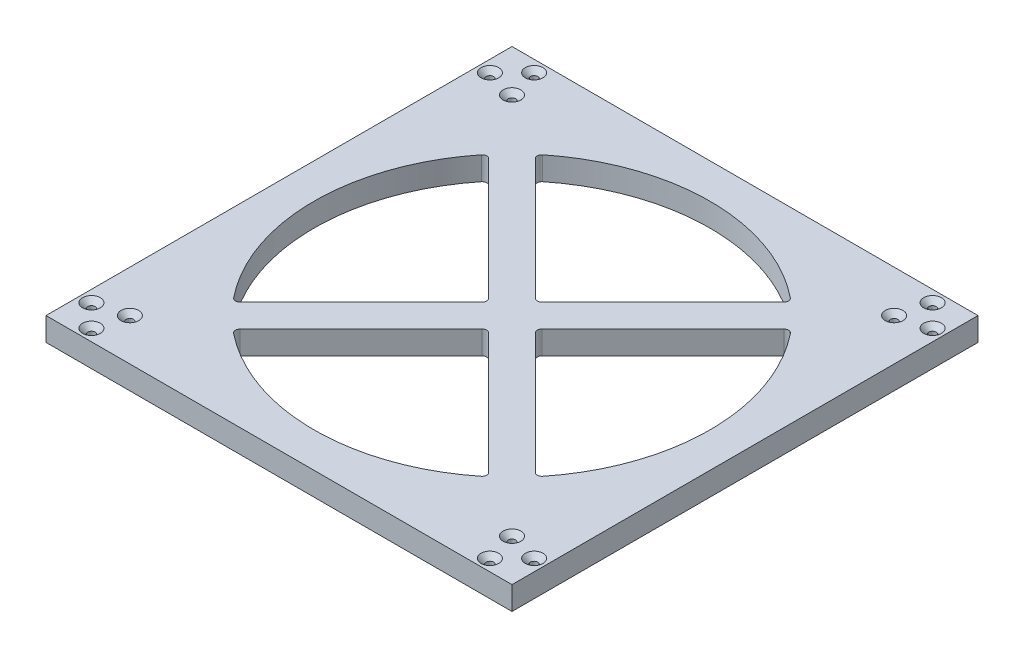
SolidWorks part; units mm, degrees
ref_plane "Front Plane" through (0, 0, 0) normal (0, 0, 1) x (1, 0, 0)
ref_plane "Top Plane" through (0, 0, 0) normal (0, 1, 0) x (1, 0, 0)
ref_plane "Right Plane" through (0, 0, 0) normal (1, 0, 0) x (0, 0, -1)
sketch "Sketch2" plane through (0, 0, 0) normal (0, 1, 0) x (1, 0, 0)
  line L0 (0, 50) -> (100, 50) construction
  line L1 (0, 0) -> (100, 0)
  line L2 (0, 0) -> (0, 100)
  line L3 (0, 100) -> (100, 100)
  line L4 (100, 0) -> (100, 100)
  line L5 (50, 0) -> (50, 100) construction
  line L14 (23.3308, 81.6692) -> (49.2929, 55.7071)
  line L15 (50.7071, 55.7071) -> (76.6692, 81.6692)
  line L16 (81.6692, 76.6692) -> (55.7071, 50.7071)
  line L17 (55.7071, 49.2929) -> (81.6692, 23.3308)
  line L18 (76.6692, 18.3308) -> (50.7071, 44.2929)
  line L19 (49.2929, 44.2929) -> (23.3308, 18.3308)
  line L20 (18.3308, 23.3308) -> (44.2929, 49.2929)
  line L21 (44.2929, 50.7071) -> (18.3308, 76.6692)
  arc A1 (76.5876, 83.1564) -> (23.4124, 83.1564) centre (50, 50) ccw
  arc A4 (49.2929, 55.7071) -> (50.7071, 55.7071) centre (50, 56.4142) ccw
  arc A5 (76.6692, 81.6692) -> (76.5876, 83.1564) centre (75.962, 82.3763) ccw
  arc A6 (23.3308, 81.6692) -> (23.4124, 83.1564) centre (24.038, 82.3763) cw
  arc A7 (83.1564, 23.4124) -> (83.1564, 76.5876) centre (50, 50) ccw
  arc A8 (55.7071, 50.7071) -> (55.7071, 49.2929) centre (56.4142, 50) ccw
  arc A9 (81.6692, 23.3308) -> (83.1564, 23.4124) centre (82.3763, 24.038) ccw
  arc A10 (81.6692, 76.6692) -> (83.1564, 76.5876) centre (82.3763, 75.962) cw
  arc A11 (23.4124, 16.8436) -> (76.5876, 16.8436) centre (50, 50) ccw
  arc A12 (50.7071, 44.2929) -> (49.2929, 44.2929) centre (50, 43.5858) ccw
  arc A13 (23.3308, 18.3308) -> (23.4124, 16.8436) centre (24.038, 17.6237) ccw
  arc A14 (76.6692, 18.3308) -> (76.5876, 16.8436) centre (75.962, 17.6237) cw
  arc A15 (16.8436, 76.5876) -> (16.8436, 23.4124) centre (50, 50) ccw
  arc A16 (44.2929, 49.2929) -> (44.2929, 50.7071) centre (43.5858, 50) ccw
  arc A17 (18.3308, 76.6692) -> (16.8436, 76.5876) centre (17.6237, 75.962) ccw
  arc A18 (18.3308, 23.3308) -> (16.8436, 23.4124) centre (17.6237, 24.038) cw
  point P16 (50, 55)
  point P50 (50, 50)
  dimension "D3" = 90
  dimension "D4" = 42.5
  dimension "D7" = 1
  dimension "D1" = 100
  dimension "D2" = 100
  dimension "D5" = 45
  dimension "D6" = 5
  dimension "D8" = 4
extrude "Boss-Extrude2" add sketch "Sketch2" along normal blind 5
sketch "Sketch3" plane through (0, 5, 0) normal (0, 1, 0) x (1, 0, 0)
  line L0 (0, 50) -> (100, 50) construction
  line L1 (0, 100) -> (0, 0) construction
  line L2 (100, 0) -> (100, 100) construction
  line L3 (50, 0) -> (50, 50) construction
  line L4 (0, 0) -> (100, 0) construction
  point P10 (9, 91)
  point P14 (91, 91)
  point P15 (91, 9)
  point P16 (9, 9)
  point P17 (50, 50)
  dimension "D1" = 41
  dimension "D2" = 41
  dimension "D3" = 4
hole_wizard "Tap Drill for M2x0.4 Tap1" positions "3DSketch1" profile "Sketch5" hole size "M2x0.4" standard "ANSI Metric" end condition through all
sketch3d "3DSketch1"
  point P0 (9, 5, -9)
  point P3 (9, 5, -91)
  point P6 (91, 5, -91)
  point P9 (91, 5, -9)
sketch "Sketch5" plane through (9, 5, -9) normal (1, 0, 0) x (0, 0, 1)
  line L0 (0, 0) -> (0, 5)
  line L1 (0, 5) -> (0.8, 5)
  line L2 (0.8, 5) -> (0.8, 1.1)
  line L3 (0.8, 1.1) -> (1.9, 0)
  line L5 (1.9, 0) -> (0, 0)
  line L6 (-0.8, 1.1) -> (-1.9, 0) construction
  line L11 (0, -6.35) -> (0, 107.95) construction
  dimension "Thru Hole Dia." = 1.6
  dimension "Thru Hole Depth" = 5
  dimension "Near C'Sink Dia." = 3.8
  dimension "Near C'Sink Angle" = 90
sketch "Sketch6" plane through (0, 5, 0) normal (0, 1, 0) x (1, 0, 0)
  line L0 (0, 0) -> (100, 0) construction
  line L1 (0, 100) -> (0, 0) construction
  point P0 (2.5, 7.25)
  point P5 (7.25, 2.5)
  dimension "D1" = 7.25
  dimension "D2" = 2.5
  dimension "D3" = 2.5
  dimension "D4" = 7.25
hole_wizard "Tap Drill for M2x0.4 Tap2" positions "3DSketch2" profile "Sketch8" hole size "M2x0.4" standard "ANSI Metric" end condition through all
sketch3d "3DSketch2"
  point P0 (2.5, 5, -7.25)
  point P3 (7.25, 5, -2.5)
sketch "Sketch8" plane through (2.5, 5, -7.25) normal (1, 0, 0) x (0, 0, 1)
  line L0 (0, 0) -> (0, 5)
  line L1 (0, 5) -> (0.8, 5)
  line L2 (0.8, 5) -> (0.8, 1.1)
  line L3 (0.8, 1.1) -> (1.9, 0)
  line L5 (1.9, 0) -> (0, 0)
  line L6 (-0.8, 1.1) -> (-1.9, 0) construction
  line L11 (0, -6.35) -> (0, 107.95) construction
  dimension "Thru Hole Dia." = 1.6
  dimension "Thru Hole Depth" = 5
  dimension "Near C'Sink Dia." = 3.8
  dimension "Near C'Sink Angle" = 90
ref_axis "Axis1" through (50, 5, -50) along (0, -1, 0)
pattern_circular "CirPattern1" count 4 over 360 about axis through (50, 5, -50) along (0, -1, 0) of "Tap Drill for M2x0.4 Tap2"
